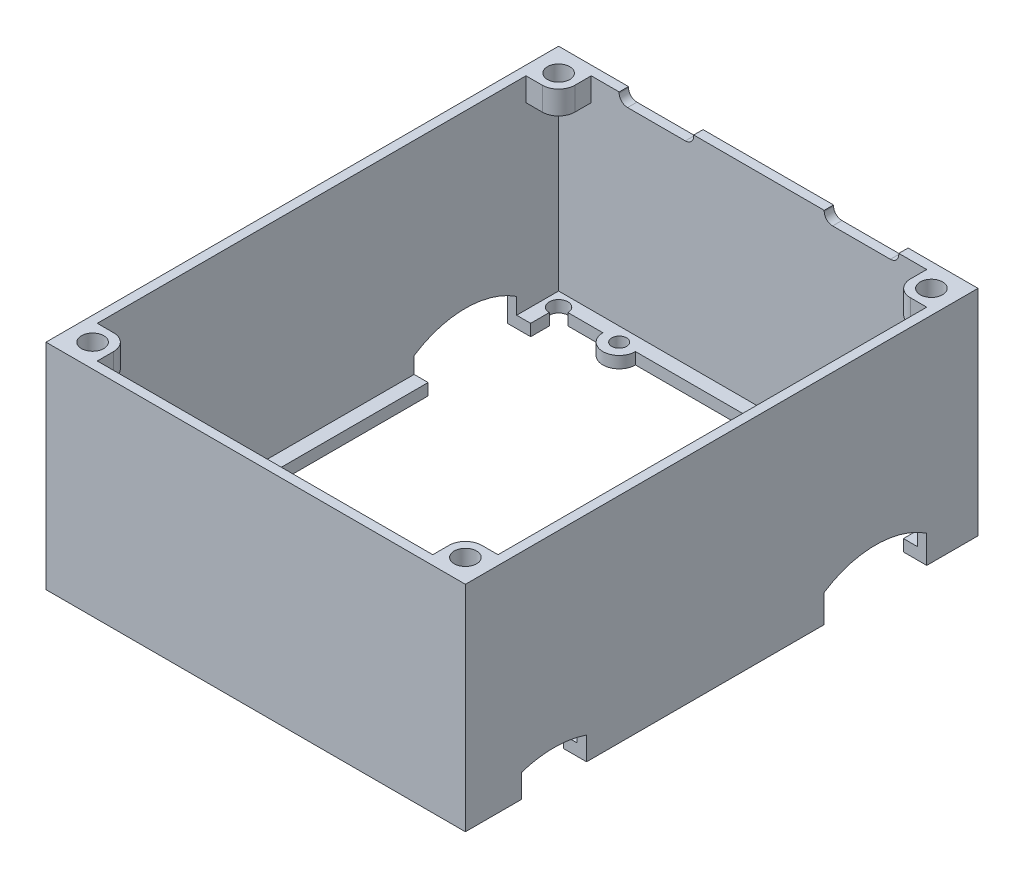
SolidWorks part; units mm, degrees
other "Markup1"
sketch "Sketch7" plane through (-45, 41, -55) normal (0, 1, 0) x (1, 0, 0)
other "DetailItem1"
ref_plane "Front Plane" through (0, 0, 0) normal (0, 0, 1) x (1, 0, 0)
ref_plane "Top Plane" through (0, 0, 0) normal (0, 1, 0) x (1, 0, 0)
ref_plane "Right Plane" through (0, 0, 0) normal (1, 0, 0) x (0, 0, -1)
sketch "Sketch1" plane through (0, 0, 0) normal (0, 1, 0) x (1, 0, 0)
  line L1 (-45, -55) -> (45, -55)
  line L2 (-45, -55) -> (-45, 55)
  line L3 (-45, 55) -> (45, 55)
  line L4 (45, -55) -> (45, 55)
  line L5 (-45, -55) -> (45, 55) construction
  line L6 (-45, 55) -> (45, -55) construction
  point P0 (0, 0)
  dimension "D1" = 90
  dimension "D2" = 110
extrude "Boss-Extrude1" add sketch "Sketch1" along normal blind 2.5
sketch "Sketch2" plane through (0, 2.5, 0) normal (0, 1, 0) x (1, 0, 0)
  line L11 (45, 55) -> (-45, 55) construction
  line L12 (-40, 50) -> (-30.5, 50)
  line L13 (-40, 50) -> (-40, -50)
  line L14 (-40, -50) -> (-25.6541, -50)
  line L15 (40, 50) -> (40, -50)
  line L16 (-40, 50) -> (40, -50) construction
  line L17 (-40, -50) -> (40, 50) construction
  line L18 (45, -55) -> (45, 55) construction
  line L19 (16.8, 50) -> (40, 50)
  line L20 (-23.5, 50) -> (9.8, 50)
  line L21 (-18.9459, -50) -> (14.8459, -50)
  line L22 (21.5541, -50) -> (40, -50)
  arc A0 (9.8, 50) -> (16.8, 50) centre (13.3, 50) ccw
  arc A1 (-18.9459, -50) -> (-25.6541, -50) centre (-22.3, -51) ccw
  arc A2 (-30.5, 50) -> (-23.5, 50) centre (-27, 50) ccw
  arc A3 (21.5541, -50) -> (14.8459, -50) centre (18.2, -51) ccw
  point P0 (0, 0)
  dimension "D4" = 7
  dimension "D6" = 7
  dimension "D1" = 5
  dimension "D2" = 5
  dimension "D3" = 13.3
  dimension "D5" = 27
  dimension "D7" = 18.2
  dimension "D8" = 22.3
  dimension "D9" = 51
extrude "Cut-Extrude1" cut sketch "Sketch2" against normal through all
sketch "Sketch6" plane through (0, 2.5, 0) normal (0, 1, 0) x (1, 0, 0)
  circle A0 centre (-27, 50) radius 1.6
  circle A1 centre (13.3, 50) radius 1.6
  circle A2 centre (18.2, -51) radius 1.6
  circle A3 centre (-22.3, -51) radius 1.6
  dimension "D1" = 3.2
extrude "Cut-Extrude4" cut sketch "Sketch6" against normal through all
sketch "Sketch3" plane through (0, 2.5, 0) normal (0, 1, 0) x (1, 0, 0)
  line L0 (45, 55) -> (-45, 55) construction
  line L1 (43, -53) -> (-43, -53)
  line L2 (43, -53) -> (43, 53)
  line L3 (43, 53) -> (-43, 53)
  line L4 (-43, -53) -> (-43, 53)
  line L5 (43, -53) -> (-43, 53) construction
  line L6 (43, 53) -> (-43, -53) construction
  line L7 (-45, 55) -> (-45, -55) construction
  point P0 (0, 0)
  line M16 (45, -55) -> (45, 55)
  line M17 (45, 55) -> (-45, 55)
  line M18 (-45, 55) -> (-45, -55)
  line M19 (-45, -55) -> (45, -55)
  dimension "D1" = 2
  dimension "D2" = 2
extrude "Boss-Extrude2" add sketch "Sketch3" along normal blind 43.5 contours L1 L4 L3 L2 M19 M16 M17 M18 region at (0, 2.5, 53.5787)
sketch "Sketch4" plane through (0, 46, 0) normal (0, 1, 0) x (1, 0, 0)
  line L1 (-43, 53) -> (-36, 53)
  line L2 (-43, 53) -> (-43, 46)
  line L3 (-43, 46) -> (-36, 46)
  line L4 (-36, 53) -> (-36, 46)
  dimension "D1" = 7
  dimension "D2" = 7
extrude "Boss-Extrude3" add sketch "Sketch4" against normal blind 5
sketch "Sketch5" plane through (0, 46, 0) normal (0, 1, 0) x (1, 0, 0)
  line L0 (45, 55) -> (-45, 55) construction
  line L1 (-45, 55) -> (-45, -55) construction
  circle A0 centre (-40, 50) radius 2.4
  dimension "D3" = 4.8
  dimension "D1" = 5
  dimension "D2" = 5
extrude "Cut-Extrude3" cut sketch "Sketch5" against normal up to next
mirror "Mirror1" about plane through (0, 0, 0) normal (1, 0, 0) of "Boss-Extrude3", "Cut-Extrude3"
mirror "Mirror2" about plane through (0, 0, 0) normal (0, 0, 1) of "Mirror1"
sketch "Sketch8" plane through (0, 2.5, 0) normal (0, 1, 0) x (1, 0, 0)
  circle A0 centre (-22.3, -51) radius 3
  circle A1 centre (18.2, -51) radius 3
  circle A2 centre (18.2, -51) radius 1.6 construction
  dimension "D1" = 6
extrude "Cut-Extrude5" cut sketch "Sketch8" along normal blind 10
sketch "Sketch9" plane through (-45, 0, 0) normal (-1, 0, 0) x (0, 0, 1)
  line L1 (-44, 6) -> (-44, 0)
  line L2 (-55, 0) -> (55, 0) construction
  line L3 (-44, 0) -> (-22, 0)
  line L4 (-22, 0) -> (-22, 6)
  line L5 (29, 0) -> (43, 0)
  line L6 (29, 0) -> (29, 5)
  line L8 (43, 0) -> (43, 5)
  arc A1 (-44, 6) -> (-22, 6) centre (-33, -10.7033) cw
  arc A2 (29, 5) -> (43, 5) centre (36, -15.8567) cw
  point P0 (-33, 0)
  point P15 (0, 0)
  point P16 (36, 0)
  dimension "D1" = 33
  dimension "D3" = 20
  dimension "D5" = 22
  dimension "D2" = 22
  dimension "D4" = 6
  dimension "D6" = 14
  dimension "D7" = 5
  dimension "D8" = 36
extrude "Cut-Extrude6" cut sketch "Sketch9" against normal through all
sketch "Sketch10" plane through (0, 0, -55) normal (0, 0, -1) x (-1, 0, 0)
  line L0 (0, 25.3) -> (0, -25.3) construction
  line L1 (-45, 46) -> (45, 46) construction
  line L2 (14, 46) -> (30, 46)
  line L3 (14, 46) -> (14, 45.8)
  line L4 (15.8, 44) -> (28.2, 44)
  line L5 (30, 46) -> (30, 45.8)
  line L6 (-30, 46) -> (-30, 45.8)
  line L7 (-15.8, 44) -> (-28.2, 44)
  line L8 (-14, 46) -> (-14, 45.8)
  line L9 (-14, 46) -> (-30, 46)
  arc A0 (28.2, 44) -> (30, 45.8) centre (28.2, 45.8) ccw
  arc A1 (14, 45.8) -> (15.8, 44) centre (15.8, 45.8) ccw
  arc A2 (-14, 45.8) -> (-15.8, 44) centre (-15.8, 45.8) cw
  arc A3 (-28.2, 44) -> (-30, 45.8) centre (-28.2, 45.8) cw
  point P7 (22, 44)
  dimension "D3" = 16
  dimension "D4" = 1.8
  dimension "D1" = 2
  dimension "D2" = 22
extrude "Cut-Extrude7" cut sketch "Sketch10" against normal up to next
sketch "Sketch12" plane through (0, 0, 0) normal (0, 1, 0) x (1, 0, 0)
  circle A0 centre (-40, -50) radius 2
  circle A1 centre (-40, -50) radius 2.4 construction
  circle A2 centre (40, -50) radius 2
  circle A3 centre (-40, 50) radius 2
  circle A4 centre (40, 50) radius 2
  circle A5 centre (-40, 50) radius 2.4 construction
  circle A6 centre (40, 50) radius 2.4 construction
  circle A7 centre (40, -50) radius 2.4 construction
  dimension "D1" = 4
extrude "Cut-Extrude8" cut sketch "Sketch12" along normal blind 5
chamfer "Chamfer1" distance 0.6 angle 60 4 edges at (40, 41, -47.6) (40, 41, 52.4) (-40, 41, 52.4) (-40, 41, -47.6) first distance on face at (40, 46, -47.6) first distance on face at (40, 41, 52.4) first distance on face at (-40, 46, 47.6) first distance on face at (-40, 41, -47.6)
fillet "Fillet1" radius 3.5 4 edges at (36, 43.5, 46) (36, 43.5, -46) (-36, 43.5, -46) (-36, 43.5, 46)
sketch "Sketch11" plane through (0, 46, 0) normal (0, 1, 0) x (1, 0, 0)
  line L1 (-34.7858, 56.1015) -> (-45.2142, 56.1015)
  line L2 (-34.7858, 56.1015) -> (-34.7858, 43.8985)
  line L3 (-34.7858, 43.8985) -> (-45.2142, 43.8985)
  line L4 (-45.2142, 56.1015) -> (-45.2142, 43.8985)
  line L5 (-34.7858, 56.1015) -> (-45.2142, 43.8985) construction
  line L6 (-34.7858, 43.8985) -> (-45.2142, 56.1015) construction
  point P0 (-40, 50)
extrude "Boss-Extrude4" [suppressed] add sketch "Sketch11" against normal blind 5 separate body
other "Intersect1" [suppressed]
equation "\"D4@Sketch2\"=\"D6@Sketch2\""
